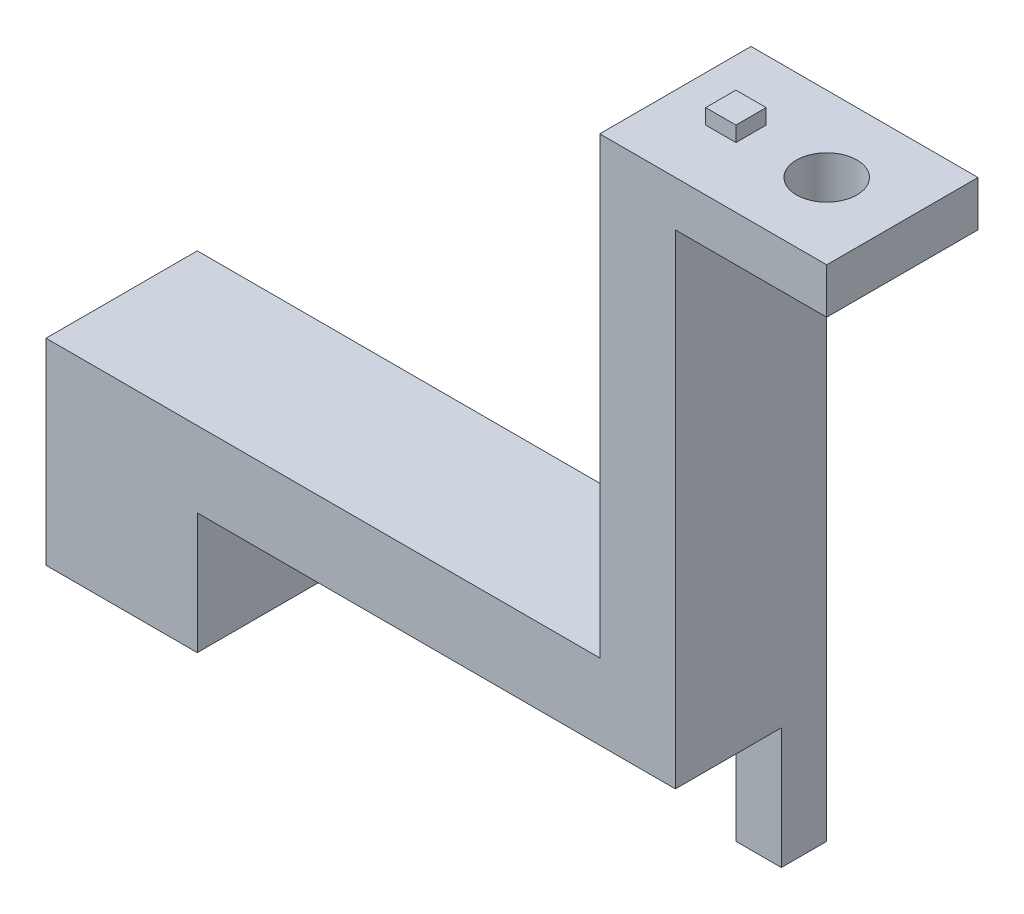
SolidWorks part; units mm, degrees
ref_plane "Front Plane" through (0, 0, 0) normal (0, 0, 1) x (1, 0, 0)
ref_plane "Top Plane" through (0, 0, 0) normal (0, 1, 0) x (1, 0, 0)
ref_plane "Right Plane" through (0, 0, 0) normal (1, 0, 0) x (0, 0, -1)
sketch "Sketch1" plane through (0, 0, 0) normal (0, 0, 1) x (1, 0, 0)
  line L0 (0, 8.6428) -> (0, -8.815) construction
  line L1 (-7.8399, 0) -> (7.1786, 0) construction
  line L2 (36.6, -2.7124) -> (36.6, 24.7717) construction
  line L3 (-5.2779, 43) -> (40.9314, 43) construction
  line L4 (10, 13) -> (36.6, 13)
  line L5 (0, 13) -> (10, 13)
  line L6 (0, 13) -> (0, 0)
  line L7 (0, 0) -> (10, 0)
  line L8 (10, 8) -> (10, 0)
  line L9 (36.6, 13) -> (36.6, 43)
  line L11 (41.6, 40) -> (41.6, 8)
  line L12 (41.6, 8) -> (10, 8)
  line L13 (41.6, 40) -> (51.6, 40)
  line L14 (51.6, 40) -> (51.6, 43)
  line L16 (36.6, 43) -> (51.6, 43)
  dimension "D4" = 30
  dimension "D1" = 36.6
  dimension "D2" = 10
  dimension "D3" = 13
  dimension "D5" = 15
  dimension "D6" = 5
  dimension "D7" = 5
  dimension "D8" = 3
  dimension "D9" = 8
extrude "Boss-Extrude1" add sketch "Sketch1" along normal blind 10
sketch "Sketch2" plane through (0, 0, 0) normal (0, -1, 0) x (1, 0, 0)
  line L0 (5, 15.6268) -> (5, -4.9051) construction
  line L1 (2.45, 6.55) -> (7.55, 6.55)
  line L2 (2.45, 6.55) -> (2.45, 3.45)
  line L3 (2.45, 3.45) -> (7.55, 3.45)
  line L4 (7.55, 6.55) -> (7.55, 3.45)
  line L5 (-4.1598, 5) -> (14.1324, 5) construction
  line L11 (0, 0) -> (10, 0) construction
  line L12 (0, 10) -> (0, 0) construction
  dimension "D1" = 5
  dimension "D2" = 5
  dimension "D3" = 5.1
  dimension "D4" = 3.1
extrude "Cut-Extrude1" cut sketch "Sketch2" against normal blind 10 contours L2 L1 L4 L3
sketch "Sketch3" plane through (0, 43, 0) normal (0, 1, 0) x (1, 0, 0)
  line L0 (29.4648, -5) -> (60.8247, -5) construction
  line L3 (51.6, 0) -> (36.6, 0) construction
  line L4 (51.6, -10) -> (51.6, 0) construction
  line L6 (39.6, -6) -> (41.6, -6)
  line L7 (39.6, -6) -> (39.6, -4)
  line L8 (39.6, -4) -> (41.6, -4)
  line L9 (41.6, -6) -> (41.6, -4)
  circle A0 centre (46.6, -5) radius 2
  dimension "D2" = 4
  dimension "D3" = 3
  dimension "D1" = 5
  dimension "D4" = 2
  dimension "D5" = 2
  dimension "D6" = 3
extrude "Boss-Extrude2" add sketch "Sketch3" along normal blind 1 contours L7 L6 L9 L8
sketch "Sketch11" plane through (0, 43, 0) normal (0, 1, 0) x (1, 0, 0)
  line L0 (29.4648, -5) -> (60.8247, -5) construction
  line L2 (51.6, -10) -> (51.6, 0) construction
  line L5 (39.6, -6) -> (41.6, -6) construction
  line L6 (39.6, -6) -> (41.6, -6)
  line L7 (39.6, -6) -> (39.6, -4)
  line L8 (39.6, -4) -> (41.6, -4)
  line L9 (41.6, -6) -> (41.6, -4)
  circle A0 centre (46.6, -5) radius 2
  dimension "D2" = 4
  dimension "D3" = 0
  dimension "D1" = 3
  dimension "D4" = 2
  dimension "D5" = 2
  dimension "D6" = 3
extrude "Cut-Extrude4" cut sketch "Sketch11" against normal up to next contours A0
sketch "Sketch12" plane through (0, 8, 0) normal (0, -1, 0) x (1, 0, 0)
  line L0 (10, 0) -> (41.6, 0) construction
  line L1 (41.6, 3) -> (38.6, 3)
  line L2 (41.6, 3) -> (41.6, 0)
  line L3 (41.6, 0) -> (38.6, 0)
  line L4 (38.6, 3) -> (38.6, 0)
  line L5 (41.6, 10) -> (41.6, 0) construction
  line L6 (60.8694, 4.3561) -> (126.3325, 4.3561)
  dimension "D1" = 3
  dimension "D2" = 3
extrude "Boss-Extrude4" add sketch "Sketch12" along normal blind 8 contours L1 L4 L0 L5 region at (40.1, 8, 1.5)
